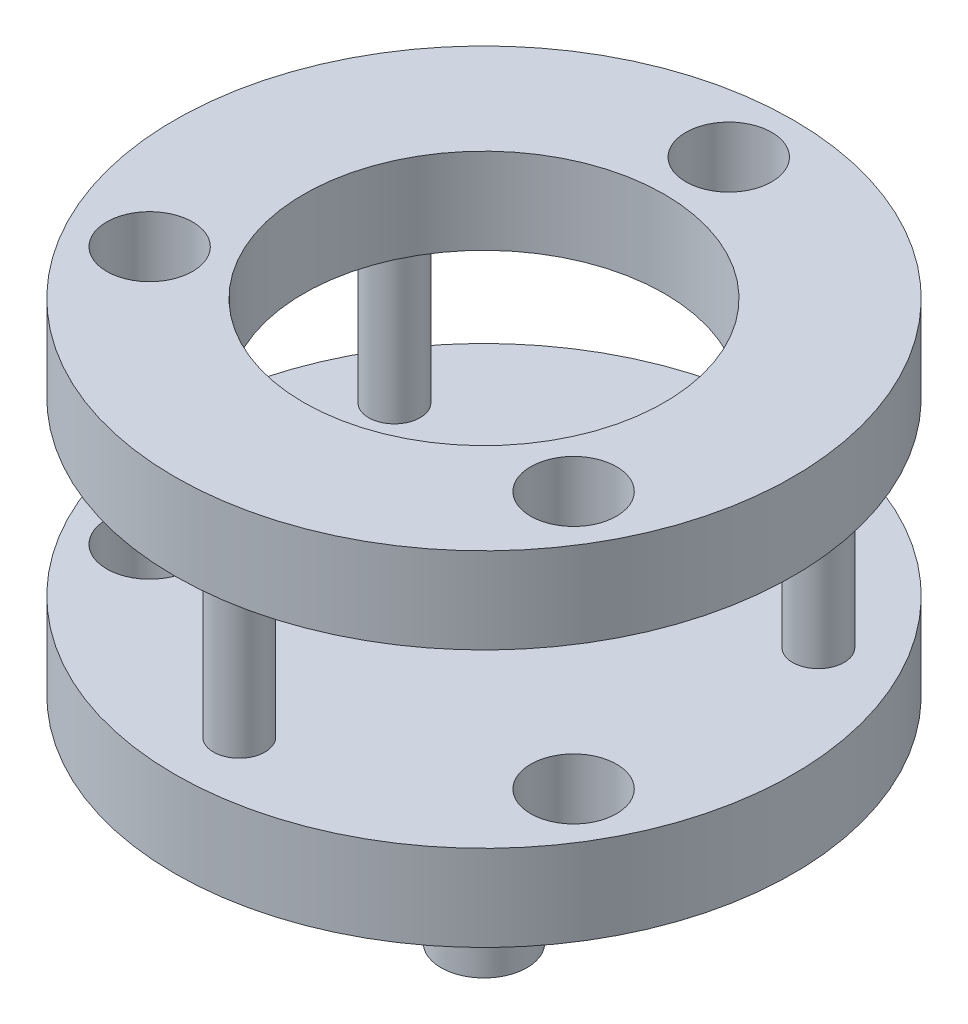
SolidWorks part; units mm, degrees
ref_plane "Front Plane" through (0, 0, 0) normal (0, 0, 1) x (1, 0, 0)
ref_plane "Top Plane" through (0, 0, 0) normal (0, 1, 0) x (1, 0, 0)
ref_plane "Right Plane" through (0, 0, 0) normal (1, 0, 0) x (0, 0, -1)
sketch "Sketch1" plane through (0, 0, 0) normal (0, 1, 0) x (1, 0, 0)
  line L0 (0, 0) -> (0, 28.5) construction
  line L1 (0, 0) -> (24.6817, -14.25) construction
  line L2 (0, 0) -> (-24.6817, -14.25) construction
  circle A0 centre (0, 0) radius 48.5
  circle A1 centre (0, 28.5) radius 5
  circle A2 centre (0, 28.5) radius 20 construction
  circle A3 centre (24.6817, -14.25) radius 20 construction
  circle A4 centre (24.6817, -14.25) radius 5
  circle A5 centre (-24.6817, -14.25) radius 20 construction
  circle A6 centre (-24.6817, -14.25) radius 5
  circle A7 centre (0, 0) radius 28.5
  circle A8 centre (0, 0) radius 21
  circle A9 centre (0, 0) radius 36
  circle A10 centre (0, -28.5) radius 3
  circle A11 centre (-24.6817, 14.25) radius 3
  circle A12 centre (24.6817, 14.25) radius 3
  point P16 (0, 0)
  point P27 (0, 0)
  dimension "D1" = 97
  dimension "D4" = 10
  dimension "D5" = 3
  dimension "D9" = 40
  dimension "D10" = 6
  dimension "D2" = 120
  dimension "D3" = 120
  dimension "D7" = 7.5
  dimension "D8" = 7.5
  dimension "D6" = 3
extrude "Boss-Extrude1" add sketch "Sketch1" along normal blind 10 contours A9 A7 A4 A6 A1 | A4 A7 A1 A6 A8 region at (0, 0, -22.6981) region at (-34.9818, 0, 0)
extrude "Boss-Extrude2" add sketch "Sketch1<3>" along normal blind 40 contours A10 | A11 | A12
sketch "Sketch1<3>" plane through (0, 0, 0) normal (0, 1, 0) x (1, 0, 0) same geometry as "Sketch1"
pattern_linear "LPattern3" count 2 spacing 30 along (0, 1, 0) of "Boss-Extrude1"
sketch "Sketch2" plane through (0, 0, 0) normal (0, -1, 0) x (1, 0, 0)
  circle A0 centre (0, 0) radius 21 construction
  circle A1 centre (0, 0) radius 21
extrude "Boss-Extrude3" add sketch "Sketch2" against normal blind 10
sketch "Sketch4" plane through (0, 0, 0) normal (0, -1, 0) x (1, 0, 0)
  circle A0 centre (0, 0) radius 5
  dimension "D1" = 10
extrude "Boss-Extrude4" add sketch "Sketch4" along normal blind 25
fillet "Fillet1" radius 10 1 edges at (0, 0, 5)
